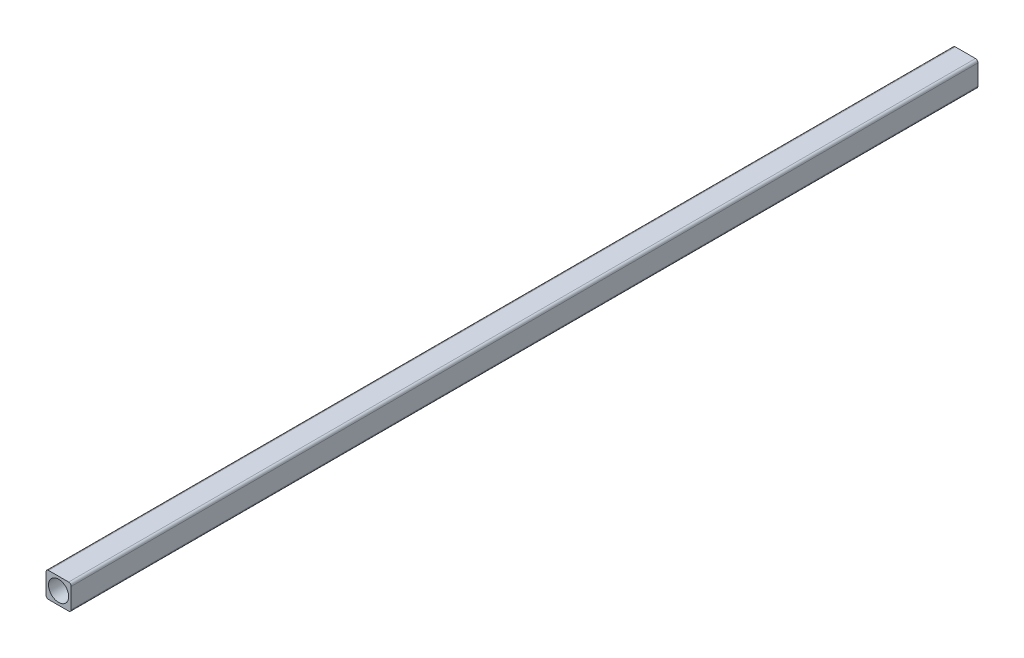
SolidWorks part; units mm, degrees
material "Hexcel AS4C (3000 Filaments)"
ref_plane "Front Plane" through (0, 0, 0) normal (0, 0, 1) x (1, 0, 0)
ref_plane "Top Plane" through (0, 0, 0) normal (0, 1, 0) x (1, 0, 0)
ref_plane "Right Plane" through (0, 0, 0) normal (1, 0, 0) x (0, 0, -1)
sketch "Sketch1" plane through (0, 0, 0) normal (0, 0, 1) x (1, 0, 0)
  line L0 (-5, -5) -> (5, -5)
  line L1 (5, -5) -> (5, 5)
  line L2 (5, 5) -> (-5, 5)
  line L3 (-5, 5) -> (-5, -5)
  circle A0 centre (0, 0) radius 4
  point P7 (-5, 0)
  point P8 (0, 5)
  dimension "D1" = 8
  dimension "D2" = 10
extrude "Boss-Extrude1" add sketch "Sketch1" along normal blind 180 and the other way blind 180
fillet "Fillet1" radius 1 4 edges at (-5, -5, 0) (5, -5, 0) (-5, 5, 0) (5, 5, 0)
